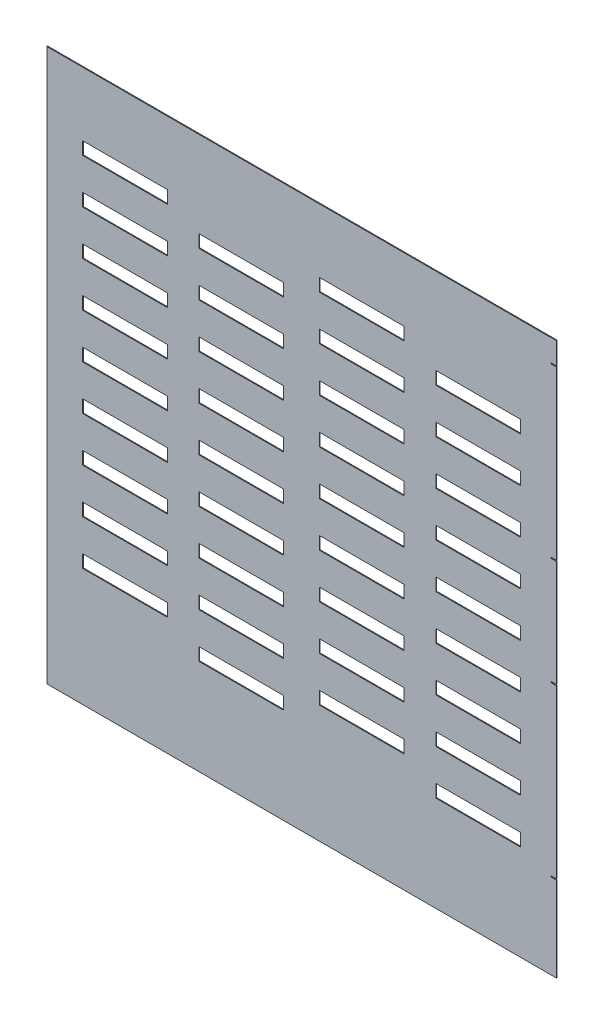
SolidWorks part; units mm, degrees
note: The reader was unsure of these and kept them because the rebuilt part matched: thickness of "Base-Flange1", "Sheet-Metal1", "Sheet-Metal2".
material "AISI 304"
ref_plane "Front Plane" through (0, 0, 0) normal (0, 0, 1) x (1, 0, 0)
ref_plane "Top Plane" through (0, 0, 0) normal (0, 1, 0) x (1, 0, 0)
ref_plane "Right Plane" through (0, 0, 0) normal (1, 0, 0) x (0, 0, -1)
sketch "Sketch1" plane through (0, 0, 0) normal (0, 0, 1) x (1, 0, 0)
  line L1 (-600, 0) -> (600, 0)
  line L2 (-600, 0) -> (-600, -1300)
  line L3 (-600, -1300) -> (600, -1300)
  line L4 (600, 0) -> (600, -1300)
  line L8 (41.7335, -150) -> (41.7335, -180)
  line L9 (-516.2066, -150) -> (-316.2066, -150)
  line L10 (-516.2066, -150) -> (-516.2066, -180)
  line L11 (-516.2066, -180) -> (-316.2066, -180)
  line L12 (-316.2066, -150) -> (-316.2066, -180)
  line L13 (41.7335, -150) -> (241.7335, -150)
  line L14 (241.7335, -150) -> (241.7335, -180)
  line L15 (41.7335, -180) -> (241.7335, -180)
  line L28 (41.7335, -255.2941) -> (41.7335, -285.2941)
  line L29 (41.7335, -255.2941) -> (241.7335, -255.2941)
  line L30 (241.7335, -255.2941) -> (241.7335, -285.2941)
  line L31 (41.7335, -285.2941) -> (241.7335, -285.2941)
  line L44 (41.7335, -360.5882) -> (41.7335, -390.5882)
  line L45 (41.7335, -360.5882) -> (241.7335, -360.5882)
  line L46 (241.7335, -360.5882) -> (241.7335, -390.5882)
  line L47 (41.7335, -390.5882) -> (241.7335, -390.5882)
  line L60 (41.7335, -465.8824) -> (41.7335, -495.8824)
  line L61 (41.7335, -465.8824) -> (241.7335, -465.8824)
  line L62 (241.7335, -465.8824) -> (241.7335, -495.8824)
  line L63 (41.7335, -495.8824) -> (241.7335, -495.8824)
  line L76 (41.7335, -571.1765) -> (41.7335, -601.1765)
  line L77 (41.7335, -571.1765) -> (241.7335, -571.1765)
  line L78 (241.7335, -571.1765) -> (241.7335, -601.1765)
  line L79 (41.7335, -601.1765) -> (241.7335, -601.1765)
  line L92 (41.7335, -676.4706) -> (41.7335, -706.4706)
  line L93 (41.7335, -676.4706) -> (241.7335, -676.4706)
  line L94 (241.7335, -676.4706) -> (241.7335, -706.4706)
  line L95 (41.7335, -706.4706) -> (241.7335, -706.4706)
  line L108 (41.7335, -781.7647) -> (41.7335, -811.7647)
  line L109 (41.7335, -781.7647) -> (241.7335, -781.7647)
  line L110 (241.7335, -781.7647) -> (241.7335, -811.7647)
  line L111 (41.7335, -811.7647) -> (241.7335, -811.7647)
  line L124 (41.7335, -887.0588) -> (41.7335, -917.0588)
  line L125 (41.7335, -887.0588) -> (241.7335, -887.0588)
  line L126 (241.7335, -887.0588) -> (241.7335, -917.0588)
  line L127 (41.7335, -917.0588) -> (241.7335, -917.0588)
  line L140 (41.7335, -992.3529) -> (41.7335, -1022.3529)
  line L141 (41.7335, -992.3529) -> (241.7335, -992.3529)
  line L142 (241.7335, -992.3529) -> (241.7335, -1022.3529)
  line L143 (41.7335, -1022.3529) -> (241.7335, -1022.3529)
  line L300 (-516.2066, -255.2941) -> (-516.2066, -285.2941)
  line L301 (-516.2066, -255.2941) -> (-316.2066, -255.2941)
  line L302 (-316.2066, -255.2941) -> (-316.2066, -285.2941)
  line L303 (-516.2066, -285.2941) -> (-316.2066, -285.2941)
  line L304 (-516.2066, -360.5882) -> (-516.2066, -390.5882)
  line L305 (-516.2066, -360.5882) -> (-316.2066, -360.5882)
  line L306 (-316.2066, -360.5882) -> (-316.2066, -390.5882)
  line L307 (-516.2066, -390.5882) -> (-316.2066, -390.5882)
  line L308 (-516.2066, -465.8824) -> (-516.2066, -495.8824)
  line L309 (-516.2066, -465.8824) -> (-316.2066, -465.8824)
  line L310 (-316.2066, -465.8824) -> (-316.2066, -495.8824)
  line L311 (-516.2066, -495.8824) -> (-316.2066, -495.8824)
  line L312 (-516.2066, -571.1765) -> (-516.2066, -601.1765)
  line L313 (-516.2066, -571.1765) -> (-316.2066, -571.1765)
  line L314 (-316.2066, -571.1765) -> (-316.2066, -601.1765)
  line L315 (-516.2066, -601.1765) -> (-316.2066, -601.1765)
  line L316 (-516.2066, -676.4706) -> (-516.2066, -706.4706)
  line L317 (-516.2066, -676.4706) -> (-316.2066, -676.4706)
  line L318 (-316.2066, -676.4706) -> (-316.2066, -706.4706)
  line L319 (-516.2066, -706.4706) -> (-316.2066, -706.4706)
  line L320 (-516.2066, -781.7647) -> (-516.2066, -811.7647)
  line L321 (-516.2066, -781.7647) -> (-316.2066, -781.7647)
  line L322 (-316.2066, -781.7647) -> (-316.2066, -811.7647)
  line L323 (-516.2066, -811.7647) -> (-316.2066, -811.7647)
  line L324 (-516.2066, -887.0588) -> (-516.2066, -917.0588)
  line L325 (-516.2066, -887.0588) -> (-316.2066, -887.0588)
  line L326 (-316.2066, -887.0588) -> (-316.2066, -917.0588)
  line L327 (-516.2066, -917.0588) -> (-316.2066, -917.0588)
  line L328 (-516.2066, -992.3529) -> (-516.2066, -1022.3529)
  line L329 (-516.2066, -992.3529) -> (-316.2066, -992.3529)
  line L330 (-316.2066, -992.3529) -> (-316.2066, -1022.3529)
  line L331 (-516.2066, -1022.3529) -> (-316.2066, -1022.3529)
  line L359 (-516.2066, -150) -> (-600, -150) construction
  line L361 (-42.0599, -232.6471) -> (-242.0599, -232.6471)
  line L362 (-42.0599, -232.6471) -> (-42.0599, -202.6471)
  line L363 (-42.0599, -202.6471) -> (-242.0599, -202.6471)
  line L364 (-242.0599, -232.6471) -> (-242.0599, -202.6471)
  line L365 (-42.0599, -232.6471) -> (-242.0599, -202.6471) construction
  line L366 (-42.0599, -202.6471) -> (-242.0599, -232.6471) construction
  line L367 (41.7335, -180) -> (41.7335, -255.2941) construction
  line L369 (-316.2066, -180) -> (41.7335, -180) construction
  line L371 (516.2066, -232.6471) -> (516.2066, -202.6471)
  line L372 (516.2066, -232.6471) -> (316.2066, -232.6471)
  line L373 (316.2066, -232.6471) -> (316.2066, -202.6471)
  line L374 (516.2066, -202.6471) -> (316.2066, -202.6471)
  line L375 (516.2066, -337.9412) -> (516.2066, -307.9412)
  line L376 (516.2066, -337.9412) -> (316.2066, -337.9412)
  line L377 (316.2066, -337.9412) -> (316.2066, -307.9412)
  line L378 (516.2066, -307.9412) -> (316.2066, -307.9412)
  line L379 (516.2066, -443.2353) -> (516.2066, -413.2353)
  line L380 (516.2066, -443.2353) -> (316.2066, -443.2353)
  line L381 (316.2066, -443.2353) -> (316.2066, -413.2353)
  line L382 (516.2066, -413.2353) -> (316.2066, -413.2353)
  line L383 (516.2066, -548.5294) -> (516.2066, -518.5294)
  line L384 (516.2066, -548.5294) -> (316.2066, -548.5294)
  line L385 (316.2066, -548.5294) -> (316.2066, -518.5294)
  line L386 (516.2066, -518.5294) -> (316.2066, -518.5294)
  line L387 (516.2066, -653.8235) -> (516.2066, -623.8235)
  line L388 (516.2066, -653.8235) -> (316.2066, -653.8235)
  line L389 (316.2066, -653.8235) -> (316.2066, -623.8235)
  line L390 (516.2066, -623.8235) -> (316.2066, -623.8235)
  line L391 (516.2066, -759.1176) -> (516.2066, -729.1176)
  line L392 (516.2066, -759.1176) -> (316.2066, -759.1176)
  line L393 (316.2066, -759.1176) -> (316.2066, -729.1176)
  line L394 (516.2066, -729.1176) -> (316.2066, -729.1176)
  line L395 (516.2066, -864.4118) -> (516.2066, -834.4118)
  line L396 (516.2066, -864.4118) -> (316.2066, -864.4118)
  line L397 (316.2066, -864.4118) -> (316.2066, -834.4118)
  line L398 (516.2066, -834.4118) -> (316.2066, -834.4118)
  line L399 (516.2066, -969.7059) -> (516.2066, -939.7059)
  line L400 (516.2066, -969.7059) -> (316.2066, -969.7059)
  line L401 (316.2066, -969.7059) -> (316.2066, -939.7059)
  line L402 (516.2066, -939.7059) -> (316.2066, -939.7059)
  line L403 (516.2066, -1075) -> (516.2066, -1045)
  line L404 (516.2066, -1075) -> (316.2066, -1075)
  line L405 (316.2066, -1075) -> (316.2066, -1045)
  line L406 (516.2066, -1045) -> (316.2066, -1045)
  line L407 (-42.0599, -337.9412) -> (-42.0599, -307.9412)
  line L408 (-42.0599, -337.9412) -> (-242.0599, -337.9412)
  line L409 (-242.0599, -337.9412) -> (-242.0599, -307.9412)
  line L410 (-42.0599, -307.9412) -> (-242.0599, -307.9412)
  line L411 (-42.0599, -443.2353) -> (-42.0599, -413.2353)
  line L412 (-42.0599, -443.2353) -> (-242.0599, -443.2353)
  line L413 (-242.0599, -443.2353) -> (-242.0599, -413.2353)
  line L414 (-42.0599, -413.2353) -> (-242.0599, -413.2353)
  line L415 (-42.0599, -548.5294) -> (-42.0599, -518.5294)
  line L416 (-42.0599, -548.5294) -> (-242.0599, -548.5294)
  line L417 (-242.0599, -548.5294) -> (-242.0599, -518.5294)
  line L418 (-42.0599, -518.5294) -> (-242.0599, -518.5294)
  line L419 (-42.0599, -653.8235) -> (-42.0599, -623.8235)
  line L420 (-42.0599, -653.8235) -> (-242.0599, -653.8235)
  line L421 (-242.0599, -653.8235) -> (-242.0599, -623.8235)
  line L422 (-42.0599, -623.8235) -> (-242.0599, -623.8235)
  line L423 (-42.0599, -759.1176) -> (-42.0599, -729.1176)
  line L424 (-42.0599, -759.1176) -> (-242.0599, -759.1176)
  line L425 (-242.0599, -759.1176) -> (-242.0599, -729.1176)
  line L426 (-42.0599, -729.1176) -> (-242.0599, -729.1176)
  line L427 (-42.0599, -864.4118) -> (-42.0599, -834.4118)
  line L428 (-42.0599, -864.4118) -> (-242.0599, -864.4118)
  line L429 (-242.0599, -864.4118) -> (-242.0599, -834.4118)
  line L430 (-42.0599, -834.4118) -> (-242.0599, -834.4118)
  line L431 (-42.0599, -969.7059) -> (-42.0599, -939.7059)
  line L432 (-42.0599, -969.7059) -> (-242.0599, -969.7059)
  line L433 (-242.0599, -969.7059) -> (-242.0599, -939.7059)
  line L434 (-42.0599, -939.7059) -> (-242.0599, -939.7059)
  line L435 (-42.0599, -1075) -> (-42.0599, -1045)
  line L436 (-42.0599, -1075) -> (-242.0599, -1075)
  line L437 (-242.0599, -1075) -> (-242.0599, -1045)
  line L438 (-42.0599, -1045) -> (-242.0599, -1045)
  line L439 (-242.0599, -969.7059) -> (-242.0599, -1045) construction
  line L441 (516.2066, -1075) -> (600, -1075) construction
  line L444 (-42.0599, -217.6471) -> (41.7335, -217.6471) construction
  point P4 (0, 0)
  point P10 (-142.0599, -217.6471)
  point P21 (41.7335, -217.6471)
  point P22 (-316.2066, -1007.3529)
  point P23 (-242.0599, -1007.3529)
  dimension "D1" = 1200
  dimension "D2" = 1300
  dimension "D3" = 200
  dimension "D4" = 30
  dimension "D5" = 150
  dimension "D6" = 925
  dimension "D7" = 2
  dimension "D8" = 9
  dimension "D10" = 2
  dimension "D11" = 9
base flange "Base-Flange1" sketch "Sketch1" thickness 2 reverse thickness direction no parameters "D1"=0.7366
sketch "Sketch2" plane through (600, 0, 0) normal (1, 0, 0) x (0, 0, -1)
  line L0 (0, 0) -> (0, -1300) construction
  line L1 (0, -51.1716) -> (2, -51.1716)
  line L2 (0, -51.1716) -> (0, -53.6716)
  line L3 (0, -53.6716) -> (2, -53.6716)
  line L4 (2, -51.1716) -> (2, -53.6716)
  line L5 (2, -1300) -> (2, 0) construction
  line L6 (0, -1300) -> (0, 0) construction
  line L7 (0, -447.7751) -> (2, -447.7751)
  line L8 (0, -447.7751) -> (0, -450.2751)
  line L9 (0, -450.2751) -> (2, -450.2751)
  line L10 (2, -447.7751) -> (2, -450.2751)
  line L12 (0, -701.2297) -> (2, -701.2297)
  line L13 (0, -701.2297) -> (0, -703.7297)
  line L14 (0, -703.7297) -> (2, -703.7297)
  line L15 (2, -701.2297) -> (2, -703.7297)
  line L16 (0, -1097.7614) -> (2, -1097.7614)
  line L17 (0, -1097.7614) -> (0, -1100.2614)
  line L18 (0, -1100.2614) -> (2, -1100.2614)
  line L19 (2, -1097.7614) -> (2, -1100.2614)
  dimension "D1" = 2.5
extrude "Cut-Extrude1" cut sketch "Sketch2" against normal blind 13 normal cut yes
fillet "Fillet1" radius 0.74 4 edges at (600, -51.1716, -1) (600, -450.2751, -1) (600, -701.2297, -1) (600, -1100.2614, -1)
sketch "Bend-Lines1" [suppressed] plane through (0, 0, 0) normal (0, 1, 0) x (1, 0, 0)
sketch "Bounding-Box1" [suppressed] plane through (0, 0, 0) normal (0, 1, 0) x (1, 0, 0)
sheet metal parameters "Sheet-Metal1" thickness 2 parameters "D1"=0.7366
flat pattern "Flat-Pattern1" [suppressed]
sketch "Bend-Lines2" plane through (0, 0, 0) normal (0, 1, 0) x (1, 0, 0)
sketch3d "Bounding-Box2" [suppressed]
  line L0 (600, 0, 0) -> (600, -1300, 0) construction
  line L1 (-600, 0, 0) -> (-600, -1300, 0) construction
  line L2 (600, 0, 0) -> (-600, 0, 0) construction
  line L3 (600, -1300, 0) -> (-600, -1300, 0) construction
sheet metal parameters "Sheet-Metal2" thickness 2 parameters "D1"=0.7366
flat pattern "Flat-Pattern1"
sketch "Bend-Lines2" plane through (0, 0, 0) normal (0, 1, 0) x (1, 0, 0)
sketch3d "Bounding-Box2" [suppressed]
  line L0 (600, 0, 0) -> (600, -1300, 0) construction
  line L1 (-600, 0, 0) -> (-600, -1300, 0) construction
  line L2 (600, 0, 0) -> (-600, 0, 0) construction
  line L3 (600, -1300, 0) -> (-600, -1300, 0) construction
equation "\"thickness 1\" = 2"
equation "\"thickness 2\"= 3"
equation "\"connecting flange\"= 35"
equation "\"main length\"= 1200"
equation "\"main width\"= 1200"
equation "\"divider panel distance offset\"= 296"
equation "\"access hatch length\" = \"access hatch cutout length\" + \"access hatch offset\" * 2"
equation "\"access hatch width\" = \"access hatch cutout width\" + \"access hatch offset\" * 2"
equation "\"side panel length\"= 1200"
equation "\"side panel width\"= 950"
equation "\"slot count x\"= 4"
equation "\"slot offset x\" = \"slot length\" + \"slot offset\""
equation "\"slot offset y\" = \"slot width\" + \"slot offset\""
equation "\"drift eliminator size offset\"= 5"
equation "\"drift eliminator depth\" = \"divider panel distance offset\""
equation "\"guide rail flange\"= 40"
equation "\"guid rail flange mount side\"= 20"
equation "\"guid rail back length\" = \"main width\" - \"guide rail flange\" * 2"
equation "\"D1@Sketch1\"=\"slotted panel width\""
equation "\"D2@Sketch1\"=\"slotted panel length\""
equation "\"D3@Sketch1\"=\"slot width\""
equation "\"D4@Sketch1\"=\"slot length\""
equation "\"D5@Sketch1\"=\"slot offset\""
equation "\"D8@Sketch1\"=\"slot count y\""
equation "\"D7@Sketch1\"=\"slot count x\"/2"
equation "\"slotted panel length\" = \"main length\" + 100"
equation "\"slotted panel width\" = \"main width\""
equation "\"slot count y\"= 9"
equation "\"slot offset\" = \"water tray depth\""
equation "\"slot length\"= 30"
equation "\"slot width\"= 200"
equation "\"thickness radius 1\"= 3.7366"
equation "\"top panel slot length\"= 250"
equation "\"top panel slot width\"= 700"
equation "\"splash plate length\"= 400"
equation "\"splash plate width\" = \"main width\""
equation "\"splash plate air gap\"= 200"
equation "\"splash plate slot count\"= 11"
equation "\"splash plate slot length\"= 50"
equation "\"splash plate slot height\"= 50"
equation "\"splash plate slot offset\"= 65"
equation "\"water tray depth\"= 150"
equation "\"water tray width\"= 200"
equation "\"dimpled panel length\" = \"main length\" - 200 - \"water tray depth\"/2"
equation "\"dimpled panel top offset\" = \"water tray depth\"/2"
equation "\"dimpled panel width\" = \"main width\""
equation "\"dimple panel slot count\"= 36"
equation "\"dimple panel slot length\"= 8"
equation "\"dimple panel slot width\"= 8"
equation "\"dimple panel slot offset\"= 25"
equation "\"sump base flat section width\"= 300"
equation "\"sump upper depth\"= 300"
equation "\"sump depth\"= 550"
equation "\"leg length\" = \"sump depth\" + 150"
equation "\"leg width\"= 80"
equation "\"leg depth\"= 40"
equation "\"leg support plate size\" = \"leg width\" - \"thickness 2\" * 2"
equation "\"leg base plate thickness\"= 8"
equation "\"thickness 3\"= 1.2"
equation "\"thichness 4\"= 0.8"
equation "\"connecting flange holes\"= 8"
equation "\"connecting flange hole gap\"= 100"
equation "\"cut out flange\"= 15"
equation "\"access hatch cutout length\"= 400"
equation "\"access hatch cutout width\"= 600"
equation "\"access hatch cutout offset X\"= 100"
equation "\"access hatch cutout offset Y\"= 100"
equation "\"access hatch offset\"= 90"
equation "\"access hatch hole\"= 9"
equation "\"access hatch hole x gap\"= 350"
equation "\"access hatch hole y gap\"= 200"
equation "\"drift eliminator cutout width\" = 1140"
equation "\"drift eliminator cutout length\" = 154"
equation "\"drift eliminator access hatch offset\" = 30"
equation "\"drift eliminator access hatch width\" = \"drift eliminator cutout width\" + \"drift eliminator access hatch offset\" * 2"
equation "\"drift eliminator access hatch length\" = \"drift eliminator cutout length\" + \"drift eliminator access hatch offset\" * 2"
equation "\"water tray panel length\"= 473"
equation "\"slot offset bottom\" = 200"
equation "\"D6@Sketch1\"=\"dimpled panel length\""
equation "\"D1@Sketch2\"=\"thickness 1\" + 0.5"
equation "\"D1@Cut-Extrude1\"=\"cut out flange\" - \"thickness 1\""
